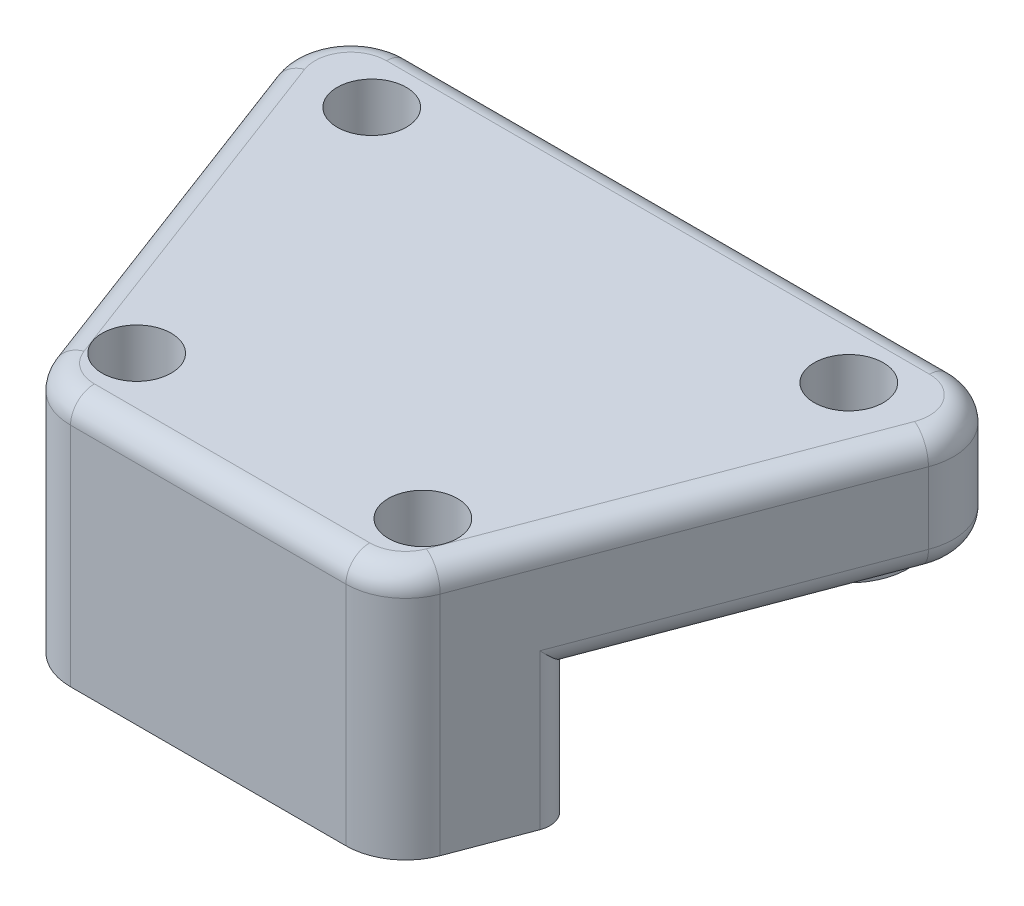
SolidWorks part; units mm, degrees
ref_plane "Спереди" through (0, 0, 0) normal (0, 0, 1) x (1, 0, 0)
ref_plane "Сверху" through (0, 0, 0) normal (0, 1, 0) x (1, 0, 0)
ref_plane "Справа" through (0, 0, 0) normal (1, 0, 0) x (0, 0, -1)
sketch "Эскиз1" plane through (0, 0, 0) normal (0, 1, 0) x (1, 0, 0)
  line L0 (0, -1011.5947) -> (0, 48988.4053) construction
  line L1 (-10, 13.8564) -> (-18, 0) construction
  line L2 (10, 13.8564) -> (18, 0) construction
  line L3 (-1018, 0) -> (48982, 0) construction
  line L4 (-15, 16.8564) -> (15, 16.8564)
  line L5 (15, 16.8564) -> (7.5, -3)
  line L6 (7.5, -3) -> (-7.5, -3)
  line L7 (-7.5, -3) -> (-15, 16.8564)
  circle A0 centre (-10, 13.8564) radius 1.45
  circle A3 centre (10, 13.8564) radius 1.45
  circle A4 centre (-6, 0) radius 1.45
  circle A5 centre (6, 0) radius 1.45
  dimension "D1" = 2.9
  dimension "D2" = 15
  dimension "D3" = 10
  dimension "D4" = 18
  dimension "D5" = 12
  dimension "D6" = 12
  dimension "D7" = 60
  dimension "D8" = 30
  dimension "D9" = 15
  dimension "D10" = 7.5
  dimension "D11" = 3
  dimension "D12" = 3
extrude "Бобышка-Вытянуть1" add sketch "Эскиз1" along normal blind 5
fillet "Скругление1" radius 2.5 4 edges at (7.5, 2.5, 3) (-7.5, 2.5, 3) (15, 2.5, -16.8564) (-15, 2.5, -16.8564)
sketch "Эскиз2" plane through (0, 0, 0) normal (0, -1, 0) x (1, 0, 0)
  circle A0 centre (-10, -13.8564) radius 1.45
  circle A1 centre (-10, -13.8564) radius 2.5
  circle A2 centre (10, -13.8564) radius 1.45
  circle A3 centre (10, -13.8564) radius 2.5
  circle A4 centre (10, -13.8564) radius 1.45 construction
  circle A5 centre (-10, -13.8564) radius 1.45 construction
  dimension "D1" = 5
extrude "Бобышка-Вытянуть2" add sketch "Эскиз2" along normal blind 0.5
sketch "Эскиз4" plane through (0, 0, 0) normal (0, -1, 0) x (1, 0, 0)
  line L0 (-5.7719, 3) -> (5.7719, 3)
  line L1 (-9.7663, -3) -> (-8.1106, 1.3834)
  line L2 (-13.7221, -13.473) -> (-8.1106, 1.3834) construction
  line L3 (-9.7663, -3) -> (9.7663, -3)
  line L4 (8.1106, 1.3834) -> (13.7221, -13.473) construction
  line L6 (8.1106, 1.3834) -> (9.7663, -3)
  arc A0 (8.1106, 1.3834) -> (5.7719, 3) centre (5.7719, 0.5) ccw construction
  arc A1 (-5.7719, 3) -> (-8.1106, 1.3834) centre (-5.7719, 0.5) ccw construction
  arc A2 (8.1106, 1.3834) -> (5.7719, 3) centre (5.7719, 0.5) ccw
  arc A3 (-5.7719, 3) -> (-8.1106, 1.3834) centre (-5.7719, 0.5) ccw
  circle A4 centre (6, 0) radius 1.45 construction
  circle A5 centre (-6, 0) radius 1.45 construction
  circle A6 centre (6, 0) radius 1.45
  circle A7 centre (-6, 0) radius 1.45
  dimension "D1" = 6
extrude "Бобышка-Вытянуть4" add sketch "Эскиз4" along normal blind 5.5
fillet "Скругление2" radius 1 15 edges at (11.7442, 0, -8.2365) (13.4398, 0, -15.778) (0, 0, -16.8564) (-13.4398, 0, -15.778) (-13.4398, 5, -15.778) (0, 5, -16.8564) (13.4398, 5, -15.778) (10.9163, 5, -6.0448) (7.1934, 5, 2.5565) (0, 5, 3) (-7.1934, 5, 2.5565) (9.7663, -2.75, -3) (-9.7663, -2.75, -3) (-11.7442, 0, -8.2365) (-10.9163, 5, -6.0448)
